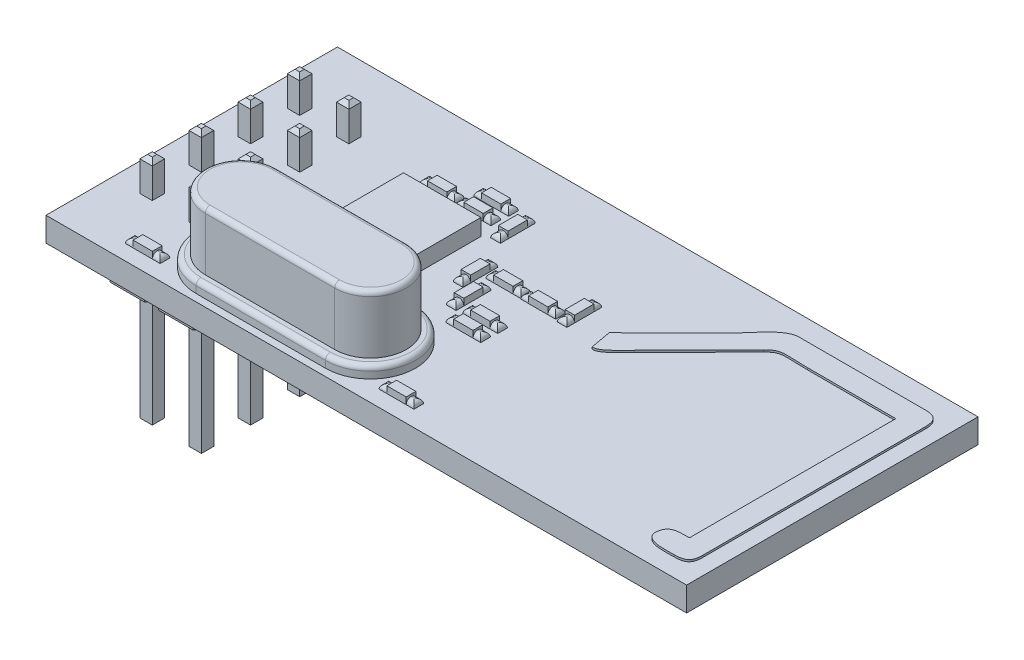
SolidWorks part; units mm, degrees
other "Camera1"
ref_plane "Front Plane" through (0, 0, 0) normal (0, 0, 1) x (1, 0, 0)
ref_plane "Top Plane" through (0, 0, 0) normal (0, 1, 0) x (1, 0, 0)
ref_plane "Right Plane" through (0, 0, 0) normal (1, 0, 0) x (0, 0, -1)
sketch "Sketch3" plane through (0, 0, 0) normal (0, 1, 0) x (1, 0, 0)
  line L1 (-99.9901, -68.9224) -> (-66.8812, -68.9224)
  line L2 (-99.9901, -68.9224) -> (-99.9901, -83.9846)
  line L3 (-99.9901, -83.9846) -> (-66.8812, -83.9846)
  line L4 (-66.8812, -68.9224) -> (-66.8812, -83.9846)
  dimension "D1" = 33.1089
  dimension "D2" = 15.0622
extrude "Boss-Extrude1" add sketch "Sketch3" along normal blind 1.25
sketch "Sketch4" plane through (0, 1.25, 0) normal (0, 1, 0) x (1, 0, 0)
  line L0 (-96.2768, -83.1974) -> (-95.2768, -83.1974)
  line L5 (-96.2768, -82.6974) -> (-96.2768, -83.1974)
  line L6 (-95.2768, -82.6974) -> (-95.2768, -83.1974)
  line L7 (-96.2768, -82.6974) -> (-95.2768, -82.6974)
  line L8 (-83.1984, -82.659) -> (-82.1984, -82.659)
  line L9 (-83.1984, -82.659) -> (-83.1984, -83.159)
  line L10 (-83.1984, -83.159) -> (-82.1984, -83.159)
  line L11 (-82.1984, -82.659) -> (-82.1984, -83.159)
  line L12 (-89.1049, -78.0894) -> (-88.1049, -78.0894)
  line L13 (-89.1049, -78.0894) -> (-89.1049, -78.5894)
  line L14 (-89.1049, -78.5894) -> (-88.1049, -78.5894)
  line L15 (-88.1049, -78.0894) -> (-88.1049, -78.5894)
  line L16 (-84.4527, -77.9524) -> (-83.4527, -77.9524)
  line L17 (-84.4527, -77.9524) -> (-84.4527, -78.4524)
  line L18 (-84.4527, -78.4524) -> (-83.4527, -78.4524)
  line L19 (-83.4527, -77.9524) -> (-83.4527, -78.4524)
  line L20 (-84.4217, -77.1047) -> (-83.4217, -77.1047)
  line L21 (-84.4217, -77.1047) -> (-84.4217, -77.6047)
  line L22 (-84.4217, -77.6047) -> (-83.4217, -77.6047)
  line L23 (-83.4217, -77.1047) -> (-83.4217, -77.6047)
  line L24 (-85.3899, -74.9435) -> (-84.3899, -74.9435)
  line L25 (-85.3899, -74.9435) -> (-85.3899, -75.4435)
  line L26 (-85.3899, -75.4435) -> (-84.3899, -75.4435)
  line L27 (-84.3899, -74.9435) -> (-84.3899, -75.4435)
  line L28 (-83.5652, -74.968) -> (-82.5652, -74.968)
  line L29 (-83.5652, -74.968) -> (-83.5652, -75.468)
  line L30 (-83.5652, -75.468) -> (-82.5652, -75.468)
  line L31 (-82.5652, -74.968) -> (-82.5652, -75.468)
  line L32 (-89.4218, -72.456) -> (-88.4218, -72.456)
  line L33 (-89.4218, -72.456) -> (-89.4218, -72.956)
  line L34 (-89.4218, -72.956) -> (-88.4218, -72.956)
  line L35 (-88.4218, -72.456) -> (-88.4218, -72.956)
  line L36 (-89.3873, -71.577) -> (-88.3873, -71.577)
  line L37 (-89.3873, -71.577) -> (-89.3873, -72.077)
  line L38 (-89.3873, -72.077) -> (-88.3873, -72.077)
  line L39 (-88.3873, -71.577) -> (-88.3873, -72.077)
  line L40 (-91.3231, -72.4336) -> (-90.3231, -72.4336)
  line L41 (-91.3231, -72.4336) -> (-91.3231, -72.9336)
  line L42 (-91.3231, -72.9336) -> (-90.3231, -72.9336)
  line L43 (-90.3231, -72.4336) -> (-90.3231, -72.9336)
  line L44 (-85.6262, -77.252) -> (-85.6262, -76.252)
  line L45 (-85.6262, -77.252) -> (-85.1262, -77.252)
  line L46 (-85.1262, -77.252) -> (-85.1262, -76.252)
  line L47 (-85.6262, -76.252) -> (-85.1262, -76.252)
  line L48 (-86.4875, -76.0362) -> (-86.4875, -75.0362)
  line L49 (-86.4875, -76.0362) -> (-85.9875, -76.0362)
  line L50 (-85.9875, -76.0362) -> (-85.9875, -75.0362)
  line L51 (-86.4875, -75.0362) -> (-85.9875, -75.0362)
  line L52 (-82.0061, -75.1458) -> (-82.0061, -74.1458)
  line L53 (-82.0061, -75.1458) -> (-81.5061, -75.1458)
  line L54 (-81.5061, -75.1458) -> (-81.5061, -74.1458)
  line L55 (-82.0061, -74.1458) -> (-81.5061, -74.1458)
  line L56 (-87.4897, -73.1009) -> (-87.4897, -72.1009)
  line L57 (-87.4897, -73.1009) -> (-86.9897, -73.1009)
  line L58 (-86.9897, -73.1009) -> (-86.9897, -72.1009)
  line L59 (-87.4897, -72.1009) -> (-86.9897, -72.1009)
  dimension "D3" = 0.5
  dimension "D4" = 1
  dimension "D5" = 0.5
  dimension "D6" = 0.5
  dimension "D7" = 0.5
  dimension "D8" = 0.5
  dimension "D9" = 0.5
  dimension "D10" = 0.5
  dimension "D11" = 0.5
  dimension "D12" = 0.5
  dimension "D13" = 0.5
  dimension "D14" = 1
  dimension "D15" = 1
  dimension "D16" = 1
  dimension "D17" = 1
extrude "Boss-Extrude2" add sketch "Sketch4" along normal blind 0.35
sketch "Sketch5" plane through (0, 1.25, 0) normal (0, 1, 0) x (1, 0, 0)
  line L0 (-82.1984, -83.159) -> (-82.1984, -82.659)
  line L1 (-83.1984, -82.659) -> (-83.1984, -83.159)
  line L2 (-82.1984, -83.159) -> (-81.7984, -83.159)
  line L3 (-83.5984, -83.159) -> (-83.1984, -83.159)
  line L4 (-83.5984, -82.659) -> (-83.5984, -83.159)
  line L5 (-81.7984, -83.159) -> (-81.7984, -82.659)
  line L6 (-83.1984, -82.659) -> (-83.5984, -82.659)
  line L7 (-82.1984, -82.659) -> (-81.7984, -82.659)
  line L8 (-84.3899, -75.4435) -> (-84.3899, -74.9435)
  line L9 (-85.3899, -74.9435) -> (-85.3899, -75.4435)
  line L10 (-84.3899, -75.4435) -> (-83.9899, -75.4435)
  line L11 (-85.7899, -75.4435) -> (-85.3899, -75.4435)
  line L12 (-85.7899, -74.9435) -> (-85.7899, -75.4435)
  line L13 (-83.9899, -75.4435) -> (-83.9899, -74.9435)
  line L14 (-85.3899, -74.9435) -> (-85.7899, -74.9435)
  line L15 (-84.3899, -74.9435) -> (-83.9899, -74.9435)
  line L16 (-82.5652, -75.468) -> (-82.5652, -74.968)
  line L17 (-83.5652, -74.968) -> (-83.5652, -75.468)
  line L18 (-82.5652, -75.468) -> (-82.1652, -75.468)
  line L19 (-83.9652, -75.468) -> (-83.5652, -75.468)
  line L20 (-83.9652, -74.968) -> (-83.9652, -75.468)
  line L21 (-82.1652, -75.468) -> (-82.1652, -74.968)
  line L22 (-83.5652, -74.968) -> (-83.9652, -74.968)
  line L23 (-82.5652, -74.968) -> (-82.1652, -74.968)
  line L24 (-90.3231, -72.9336) -> (-90.3231, -72.4336)
  line L25 (-91.3231, -72.4336) -> (-91.3231, -72.9336)
  line L26 (-90.3231, -72.9336) -> (-89.9231, -72.9336)
  line L27 (-91.7231, -72.9336) -> (-91.3231, -72.9336)
  line L28 (-91.7231, -72.4336) -> (-91.7231, -72.9336)
  line L29 (-89.9231, -72.9336) -> (-89.9231, -72.4336)
  line L30 (-91.3231, -72.4336) -> (-91.7231, -72.4336)
  line L31 (-90.3231, -72.4336) -> (-89.9231, -72.4336)
  line L32 (-88.4218, -72.956) -> (-88.4218, -72.456)
  line L33 (-89.4218, -72.456) -> (-89.4218, -72.956)
  line L34 (-88.4218, -72.956) -> (-88.0218, -72.956)
  line L35 (-89.8218, -72.956) -> (-89.4218, -72.956)
  line L36 (-89.8218, -72.456) -> (-89.8218, -72.956)
  line L37 (-88.0218, -72.956) -> (-88.0218, -72.456)
  line L38 (-89.4218, -72.456) -> (-89.8218, -72.456)
  line L39 (-88.4218, -72.456) -> (-88.0218, -72.456)
  line L40 (-88.3873, -72.077) -> (-88.3873, -71.577)
  line L41 (-89.3873, -71.577) -> (-89.3873, -72.077)
  line L42 (-88.3873, -72.077) -> (-87.9873, -72.077)
  line L43 (-89.7873, -72.077) -> (-89.3873, -72.077)
  line L44 (-89.7873, -71.577) -> (-89.7873, -72.077)
  line L45 (-87.9873, -72.077) -> (-87.9873, -71.577)
  line L46 (-89.3873, -71.577) -> (-89.7873, -71.577)
  line L47 (-88.3873, -71.577) -> (-87.9873, -71.577)
  line L48 (-86.9897, -72.1009) -> (-87.4897, -72.1009)
  line L49 (-87.4897, -73.1009) -> (-86.9897, -73.1009)
  line L50 (-86.9897, -72.1009) -> (-86.9897, -71.7009)
  line L51 (-86.9897, -73.5009) -> (-86.9897, -73.1009)
  line L52 (-87.4897, -73.5009) -> (-86.9897, -73.5009)
  line L53 (-96.2768, -82.6974) -> (-96.2768, -83.1974) construction
  line L54 (-86.9897, -71.7009) -> (-87.4897, -71.7009)
  line L55 (-95.2768, -83.1974) -> (-95.2768, -82.6974) construction
  line L56 (-88.1049, -78.5894) -> (-88.1049, -78.0894)
  line L57 (-89.1049, -78.0894) -> (-89.1049, -78.5894)
  line L58 (-88.1049, -78.5894) -> (-87.7049, -78.5894)
  line L59 (-89.5049, -78.5894) -> (-89.1049, -78.5894)
  line L60 (-89.5049, -78.0894) -> (-89.5049, -78.5894)
  line L61 (-87.7049, -78.5894) -> (-87.7049, -78.0894)
  line L62 (-89.1049, -78.0894) -> (-89.5049, -78.0894)
  line L63 (-88.1049, -78.0894) -> (-87.7049, -78.0894)
  line L64 (-83.4217, -77.6047) -> (-83.4217, -77.1047)
  line L65 (-83.4217, -77.6047) -> (-83.0217, -77.6047)
  line L66 (-83.4217, -77.1047) -> (-83.0217, -77.1047)
  line L67 (-84.8217, -77.1047) -> (-84.8217, -77.6047)
  line L68 (-84.8217, -77.6047) -> (-84.4217, -77.6047)
  line L69 (-83.0217, -77.6047) -> (-83.0217, -77.1047)
  line L70 (-84.4217, -77.1047) -> (-84.4217, -77.6047)
  line L71 (-84.4217, -77.1047) -> (-84.8217, -77.1047)
  line L72 (-83.4527, -78.4524) -> (-83.4527, -77.9524)
  line L73 (-84.4527, -77.9524) -> (-84.4527, -78.4524)
  line L74 (-83.4527, -78.4524) -> (-83.0527, -78.4524)
  line L75 (-84.8527, -78.4524) -> (-84.4527, -78.4524)
  line L76 (-84.8527, -77.9524) -> (-84.8527, -78.4524)
  line L77 (-83.0527, -78.4524) -> (-83.0527, -77.9524)
  line L78 (-84.4527, -77.9524) -> (-84.8527, -77.9524)
  line L79 (-83.4527, -77.9524) -> (-83.0527, -77.9524)
  line L80 (-87.4897, -73.1009) -> (-87.4897, -73.5009)
  line L81 (-87.4897, -72.1009) -> (-87.4897, -71.7009)
  line L82 (-81.5061, -74.1458) -> (-82.0061, -74.1458)
  line L83 (-82.0061, -75.1458) -> (-81.5061, -75.1458)
  line L84 (-81.5061, -74.1458) -> (-81.5061, -73.7458)
  line L85 (-81.5061, -75.5458) -> (-81.5061, -75.1458)
  line L86 (-82.0061, -75.5458) -> (-81.5061, -75.5458)
  line L87 (-81.5061, -73.7458) -> (-82.0061, -73.7458)
  line L88 (-82.0061, -75.1458) -> (-82.0061, -75.5458)
  line L89 (-82.0061, -74.1458) -> (-82.0061, -73.7458)
  line L90 (-85.6262, -77.652) -> (-85.1262, -77.652)
  line L91 (-85.1262, -75.852) -> (-85.6262, -75.852)
  line L92 (-85.6262, -77.252) -> (-85.6262, -77.652)
  line L93 (-85.1262, -76.252) -> (-85.6262, -76.252)
  line L94 (-85.6262, -76.252) -> (-85.6262, -75.852)
  line L95 (-85.6262, -77.252) -> (-85.1262, -77.252)
  line L96 (-85.1262, -76.252) -> (-85.1262, -75.852)
  line L97 (-85.1262, -77.652) -> (-85.1262, -77.252)
  line L98 (-85.9875, -76.4362) -> (-85.9875, -76.0362)
  line L99 (-85.9875, -74.6362) -> (-86.4875, -74.6362)
  line L100 (-86.4875, -76.4362) -> (-85.9875, -76.4362)
  line L101 (-86.4875, -76.0362) -> (-86.4875, -76.4362)
  line L102 (-86.4875, -75.0362) -> (-86.4875, -74.6362)
  line L103 (-85.9875, -75.0362) -> (-86.4875, -75.0362)
  line L104 (-86.4875, -76.0362) -> (-85.9875, -76.0362)
  line L105 (-85.9875, -75.0362) -> (-85.9875, -74.6362)
  line L109 (-96.2768, -82.6974) -> (-96.2768, -83.1974)
  line L111 (-95.2768, -83.1974) -> (-95.2768, -82.6974)
  line L113 (-96.6768, -82.6974) -> (-96.6768, -83.1974)
  line L114 (-94.8768, -83.5974) -> (-94.8768, -82.2974) construction
  line L115 (-94.8768, -83.1974) -> (-94.8768, -82.6974)
  line L116 (-96.2768, -82.6974) -> (-96.6768, -82.6974)
  line L117 (-96.6768, -83.1974) -> (-96.2768, -83.1974)
  line L118 (-95.2768, -82.6974) -> (-94.8768, -82.6974)
  line L119 (-95.2768, -83.1974) -> (-94.8768, -83.1974)
  line L120 (-96.6768, -82.2974) -> (-96.6768, -83.5974) construction
  line L121 (-94.8768, -82.2974) -> (-96.6768, -82.2974) construction
  line L122 (-96.6768, -83.5974) -> (-94.8768, -83.5974) construction
  line L123 (-95.2768, -82.6974) -> (-96.2768, -82.6974) construction
  line L124 (-96.2768, -83.1974) -> (-95.2768, -83.1974) construction
  dimension "D1" = 0.4
extrude "Boss-Extrude4" add sketch "Sketch5" along normal blind 0.25
fillet "Fillet3" radius 0.25 84 edges at (-94.8768, 1.5, 82.9474) (-95.0768, 1.5, 82.6974) (-95.0768, 1.5, 83.1974) (-91.5231, 1.5, 72.4336) (-91.7231, 1.5, 72.6836) (-91.5231, 1.5, 72.9336) (-89.9231, 1.5, 72.6836) (-90.1231, 1.5, 72.4336) (-90.1231, 1.5, 72.9336) (-89.5873, 1.5, 71.577) (-89.7873, 1.5, 71.827) (-89.5873, 1.5, 72.077) (-89.6218, 1.5, 72.456) (-89.8218, 1.5, 72.706) (-89.6218, 1.5, 72.956) (-88.1873, 1.5, 71.577) (-87.9873, 1.5, 71.827) (-88.1873, 1.5, 72.077) (-88.2218, 1.5, 72.456) (-88.0218, 1.5, 72.706) (-88.2218, 1.5, 72.956) (-86.9897, 1.5, 71.9009) (-87.2397, 1.5, 71.7009) (-87.4897, 1.5, 71.9009) (-86.9897, 1.5, 73.3009) (-87.2397, 1.5, 73.5009) (-87.4897, 1.5, 73.3009) (-81.5061, 1.5, 73.9458) (-81.7561, 1.5, 73.7458) (-82.0061, 1.5, 73.9458) (-81.5061, 1.5, 75.3458) (-81.7561, 1.5, 75.5458) (-82.0061, 1.5, 75.3458) (-82.3652, 1.5, 74.968) (-82.1652, 1.5, 75.218) (-82.3652, 1.5, 75.468) (-83.7652, 1.5, 75.468) (-83.9652, 1.5, 75.218) (-83.7652, 1.5, 74.968) (-84.1899, 1.5, 74.9435) (-83.9899, 1.5, 75.1935) (-84.1899, 1.5, 75.4435) (-85.5899, 1.5, 74.9435) (-85.5899, 1.5, 75.4435) (-85.7899, 1.5, 75.1935) (-85.9875, 1.5, 74.8362) (-86.2375, 1.5, 74.6362) (-86.4875, 1.5, 74.8362) (-85.9875, 1.5, 76.2362) (-86.2375, 1.5, 76.4362) (-86.4875, 1.5, 76.2362) (-85.1262, 1.5, 76.052) (-85.3762, 1.5, 75.852) (-85.6262, 1.5, 76.052) (-83.2217, 1.5, 77.1047) (-83.0217, 1.5, 77.3547) (-83.2217, 1.5, 77.6047) (-83.2527, 1.5, 77.9524) (-83.0527, 1.5, 78.2024) (-83.2527, 1.5, 78.4524) (-85.6262, 1.5, 77.452) (-85.1262, 1.5, 77.452) (-85.3762, 1.5, 77.652) (-84.6217, 1.5, 77.1047) (-84.6217, 1.5, 77.6047) (-84.8217, 1.5, 77.3547) (-84.6527, 1.5, 77.9524) (-84.6527, 1.5, 78.4524) (-84.8527, 1.5, 78.2024) (-87.9049, 1.5, 78.0894) (-87.7049, 1.5, 78.3394) (-87.9049, 1.5, 78.5894) (-89.3049, 1.5, 78.0894) (-89.5049, 1.5, 78.3394) (-89.3049, 1.5, 78.5894) (-81.9984, 1.5, 82.659) (-81.7984, 1.5, 82.909) (-81.9984, 1.5, 83.159) (-83.3984, 1.5, 82.659) (-83.5984, 1.5, 82.909) (-83.3984, 1.5, 83.159) (-96.6768, 1.5, 82.9474) (-96.4768, 1.5, 82.6974) (-96.4768, 1.5, 83.1974)
sketch "Sketch6" plane through (0, 1.25, 0) normal (0, 1, 0) x (1, 0, 0)
  line L1 (-87.8017, -77.6945) -> (-91.8017, -77.6945)
  line L2 (-87.8017, -77.6945) -> (-87.8017, -73.6945)
  line L3 (-87.8017, -73.6945) -> (-91.8017, -73.6945)
  line L4 (-91.8017, -77.6945) -> (-91.8017, -73.6945)
  dimension "D1" = 4
  dimension "D2" = 4
extrude "Boss-Extrude5" add sketch "Sketch6" along normal blind 0.85
sketch "Sketch7" plane through (0, 1.25, 0) normal (0, 1, 0) x (1, 0, 0)
  line L0 (-92.6052, -81.2861) -> (-85.9152, -81.2861) construction
  line L1 (-92.6052, -78.9611) -> (-85.9152, -78.9611)
  line L2 (-92.6052, -83.6111) -> (-85.9152, -83.6111)
  arc A0 (-92.6052, -78.9611) -> (-92.6052, -83.6111) centre (-92.6052, -81.2861) ccw
  arc A1 (-85.9152, -83.6111) -> (-85.9152, -78.9611) centre (-85.9152, -81.2861) ccw
  point P2 (-89.2602, -81.2861)
  dimension "D2" = 6.69
  dimension "D1" = 4.65
extrude "Boss-Extrude6" add sketch "Sketch7" along normal blind 0.6
sketch "Sketch8" plane through (0, 1.85, 0) normal (0, 1, 0) x (1, 0, 0)
  line L0 (-92.6052, -78.9611) -> (-92.6052, -83.6111) construction
  line L1 (-92.6052, -83.6111) -> (-85.9152, -78.9611) construction
  line L2 (-85.9152, -78.9611) -> (-85.9152, -83.6111) construction
  line L3 (-85.9152, -83.6111) -> (-85.9152, -81.2861) construction
  line L4 (-85.9152, -81.2861) -> (-92.6052, -81.2861) construction
  line L5 (-92.6052, -81.2861) -> (-85.9152, -81.2861) construction
  line L6 (-92.6052, -79.4361) -> (-85.9152, -79.4361)
  line L7 (-92.6052, -83.1361) -> (-85.9152, -83.1361)
  arc A0 (-85.9152, -83.6111) -> (-85.9152, -78.9611) centre (-85.9152, -81.2861) ccw construction
  arc A1 (-92.6052, -79.4361) -> (-92.6052, -83.1361) centre (-92.6052, -81.2861) ccw
  arc A2 (-85.9152, -83.1361) -> (-85.9152, -79.4361) centre (-85.9152, -81.2861) ccw
  point P13 (-89.2602, -81.2861)
  dimension "D1" = 3.7
extrude "Boss-Extrude7" add sketch "Sketch8" along normal blind 3
fillet "Fillet4" radius 0.25 8 edges at (-89.2602, 1.85, 78.9611) (-83.5902, 1.85, 81.2861) (-89.2602, 1.85, 83.6111) (-89.2602, 4.85, 79.4361) (-84.0652, 4.85, 81.2861) (-89.2602, 4.85, 83.1361) (-94.4552, 4.85, 81.2861) (-94.9302, 1.85, 81.2861)
sketch "Sketch9" plane through (0, 1.25, 0) normal (0, 1, 0) x (1, 0, 0)
  line L0 (-97.3427, -73.9134) -> (-96.9892, -73.5599)
  line L1 (-96.9892, -73.5599) -> (-96.6356, -73.9134)
  line L2 (-96.6356, -73.9134) -> (-94.8427, -73.9134)
  line L3 (-94.8427, -73.9134) -> (-94.4892, -73.5599)
  line L4 (-94.4892, -73.5599) -> (-94.4892, -71.726)
  line L5 (-94.4892, -71.726) -> (-94.8427, -71.3724)
  line L6 (-94.8427, -71.3724) -> (-96.6356, -71.3724)
  line L7 (-96.6356, -71.3724) -> (-96.9892, -71.726)
  line L8 (-96.9892, -71.726) -> (-97.3427, -71.3724)
  line L9 (-97.3427, -71.3724) -> (-99.1356, -71.3724)
  line L10 (-99.1356, -71.3724) -> (-99.4892, -71.726)
  line L11 (-99.4892, -71.726) -> (-99.4892, -73.5599)
  line L12 (-99.4892, -73.5599) -> (-99.1356, -73.9134)
  line L13 (-99.1356, -73.9134) -> (-97.3427, -73.9134)
  line L15 (-66.8812, -68.9224) -> (-99.9901, -68.9224) construction
  dimension "D1" = 2.45
extrude "Boss-Extrude10" add sketch "Sketch9" against normal blind 3.79
pattern_linear "LPattern1" count 4 spacing 2.54 along (0, 0, 1) of "Boss-Extrude10"
sketch "Sketch11" plane through (0, 0, 0) normal (0, 1, 0) x (1, 0, 0)
  line L13 (-80.0785, -74.7818) -> (-79.8827, -75.8652)
  line L44 (-78.6389, -74.9196) -> (-75.3174, -71.5648)
  line L45 (-68.8239, -71.2274) -> (-68.8239, -81.8943)
  line L46 (-67.6982, -82.3293) -> (-67.6982, -70.8178)
  line L47 (-68.4656, -70.0758) -> (-74.9887, -70.0758)
  line L48 (-76.6578, -71.3745) -> (-79.6894, -74.4056)
  spline S82 degree 3 poles (-79.8827, -75.8652) (-79.4789, -75.9086) (-78.9112, -75.1567) (-78.6389, -74.9196) knots 0.190476 0.190476 0.190476 0.190476 0.238095 0.238095 0.238095 0.238095
  spline S83 degree 3 poles (-75.3174, -71.5648) (-74.8372, -71.0611) (-74.6535, -71.2274) (-73.3771, -71.2274) knots 0.285714 0.285714 0.285714 0.285714 0.333333 0.333333 0.333333 0.333333
  spline S84 degree 3 poles (-73.3771, -71.2274) (-71.8594, -71.2274) (-70.3416, -71.2274) (-68.8239, -71.2274) knots 0.333333 0.333333 0.333333 0.333333 0.380952 0.380952 0.380952 0.380952
  spline S85 degree 3 poles (-68.8239, -81.8943) (-69.3337, -81.8943) (-69.7736, -81.865) (-69.9071, -82.2846) knots 0.428571 0.428571 0.428571 0.428571 0.47619 0.47619 0.47619 0.47619
  spline S86 degree 3 poles (-69.9071, -82.2846) (-70.1923, -83.1815) (-68.9534, -83.0454) (-68.4656, -83.0454) knots 0.47619 0.47619 0.47619 0.47619 0.52381 0.52381 0.52381 0.52381
  spline S87 degree 3 poles (-68.4656, -83.0454) (-67.9097, -83.0454) (-67.6982, -82.8768) (-67.6982, -82.3293) knots 0.52381 0.52381 0.52381 0.52381 0.571429 0.571429 0.571429 0.571429
  spline S88 degree 3 poles (-67.6982, -70.8178) (-67.6982, -70.2715) (-67.9312, -70.0758) (-68.4656, -70.0758) knots 0.619048 0.619048 0.619048 0.619048 0.666667 0.666667 0.666667 0.666667
  spline S89 degree 3 poles (-74.9887, -70.0758) (-75.6518, -70.0758) (-76.3059, -71.0155) (-76.6578, -71.3745) knots 0.714286 0.714286 0.714286 0.714286 0.761905 0.761905 0.761905 0.761905
  spline S90 degree 3 poles (-79.6894, -74.4056) (-79.8367, -74.5533) (-79.9262, -74.6298) (-80.0785, -74.7818) knots 0.809524 0.809524 0.809524 0.809524 0.857143 0.857143 0.857143 0.857143
extrude "Boss-Extrude12" add sketch "Sketch11" along normal blind 1.35
sketch "Sketch12" plane through (0, -2.54, 0) normal (0, -1, 0) x (1, 0, 0)
  line L0 (-99.1356, 81.5334) -> (-97.3427, 81.5334) construction
  line L1 (-98.5392, 80.5834) -> (-97.8992, 80.5834)
  line L2 (-98.5392, 80.5834) -> (-98.5392, 79.9434)
  line L3 (-98.5392, 79.9434) -> (-97.8992, 79.9434)
  line L4 (-97.8992, 80.5834) -> (-97.8992, 79.9434)
  line L5 (-99.4892, 79.346) -> (-99.4892, 81.1799) construction
  line L6 (-95.9992, 80.5834) -> (-95.3592, 80.5834)
  line L7 (-95.9992, 80.5834) -> (-95.9992, 79.9434)
  line L8 (-95.9992, 79.9434) -> (-95.3592, 79.9434)
  line L9 (-95.3592, 80.5834) -> (-95.3592, 79.9434)
  line L10 (-95.9992, 78.0434) -> (-95.3592, 78.0434)
  line L11 (-95.9992, 78.0434) -> (-95.9992, 77.4034)
  line L12 (-95.9992, 77.4034) -> (-95.3592, 77.4034)
  line L13 (-95.3592, 78.0434) -> (-95.3592, 77.4034)
  line L14 (-95.9992, 75.5034) -> (-95.3592, 75.5034)
  line L15 (-95.9992, 75.5034) -> (-95.9992, 74.8634)
  line L16 (-95.9992, 74.8634) -> (-95.3592, 74.8634)
  line L17 (-95.3592, 75.5034) -> (-95.3592, 74.8634)
  line L18 (-95.9992, 72.9634) -> (-95.3592, 72.9634)
  line L19 (-95.9992, 72.9634) -> (-95.9992, 72.3234)
  line L20 (-95.9992, 72.3234) -> (-95.3592, 72.3234)
  line L21 (-95.3592, 72.9634) -> (-95.3592, 72.3234)
  line L22 (-98.5392, 78.0434) -> (-97.8992, 78.0434)
  line L23 (-98.5392, 78.0434) -> (-98.5392, 77.4034)
  line L24 (-98.5392, 77.4034) -> (-97.8992, 77.4034)
  line L25 (-97.8992, 78.0434) -> (-97.8992, 77.4034)
  line L26 (-98.5392, 75.5034) -> (-97.8992, 75.5034)
  line L27 (-98.5392, 75.5034) -> (-98.5392, 74.8634)
  line L28 (-98.5392, 74.8634) -> (-97.8992, 74.8634)
  line L29 (-97.8992, 75.5034) -> (-97.8992, 74.8634)
  line L30 (-98.5392, 72.9634) -> (-97.8992, 72.9634)
  line L31 (-98.5392, 72.9634) -> (-98.5392, 72.3234)
  line L32 (-98.5392, 72.3234) -> (-97.8992, 72.3234)
  line L33 (-97.8992, 72.9634) -> (-97.8992, 72.3234)
  dimension "D1" = 0.64
  dimension "D2" = 0.95
  dimension "D3" = 0.95
  dimension "D4" = 2
  dimension "D5" = 4
extrude "Boss-Extrude13" add sketch "Sketch12" against normal blind 5.54 and the other way blind 6.46
chamfer "Chamfer1" distance 0.2 angle 45 64 edges at (-98.2192, -9, 80.5834) (-97.8992, -9, 80.2634) (-98.2192, -9, 79.9434) (-98.5392, -9, 80.2634) (-95.6792, -9, 80.5834) (-95.3592, -9, 80.2634) (-95.6792, -9, 79.9434) (-95.9992, -9, 80.2634) (-98.2192, -9, 78.0434) (-97.8992, -9, 77.7234) (-98.2192, -9, 77.4034) (-98.5392, -9, 77.7234) (-95.6792, -9, 78.0434) (-95.3592, -9, 77.7234) (-95.6792, -9, 77.4034) (-95.9992, -9, 77.7234) (-98.2192, -9, 75.5034) (-97.8992, -9, 75.1834) (-98.2192, -9, 74.8634) (-98.5392, -9, 75.1834) (-95.6792, -9, 75.5034) (-95.3592, -9, 75.1834) (-95.6792, -9, 74.8634) (-95.9992, -9, 75.1834) (-95.6792, -9, 72.9634) (-95.3592, -9, 72.6434) (-95.6792, -9, 72.3234) (-95.9992, -9, 72.6434) (-98.2192, -9, 72.9634) (-97.8992, -9, 72.6434) (-98.2192, -9, 72.3234) (-98.5392, -9, 72.6434) (-98.2192, 3, 72.3234) (-97.8992, 3, 72.6434) (-98.2192, 3, 72.9634) (-98.5392, 3, 72.6434) (-95.6792, 3, 72.3234) (-95.3592, 3, 72.6434) (-95.6792, 3, 72.9634) (-95.9992, 3, 72.6434) (-95.6792, 3, 74.8634) (-95.3592, 3, 75.1834) (-95.6792, 3, 75.5034) (-95.9992, 3, 75.1834) (-98.2192, 3, 74.8634) (-97.8992, 3, 75.1834) (-98.2192, 3, 75.5034) (-98.5392, 3, 75.1834) (-98.2192, 3, 77.4034) (-97.8992, 3, 77.7234) (-98.2192, 3, 78.0434) (-98.5392, 3, 77.7234) (-95.6792, 3, 77.4034) (-95.3592, 3, 77.7234) (-95.6792, 3, 78.0434) (-95.9992, 3, 77.7234) (-95.6792, 3, 79.9434) (-95.3592, 3, 80.2634) (-95.6792, 3, 80.5834) (-95.9992, 3, 80.2634) (-98.2192, 3, 79.9434) (-97.8992, 3, 80.2634) (-98.2192, 3, 80.5834) (-98.5392, 3, 80.2634)
